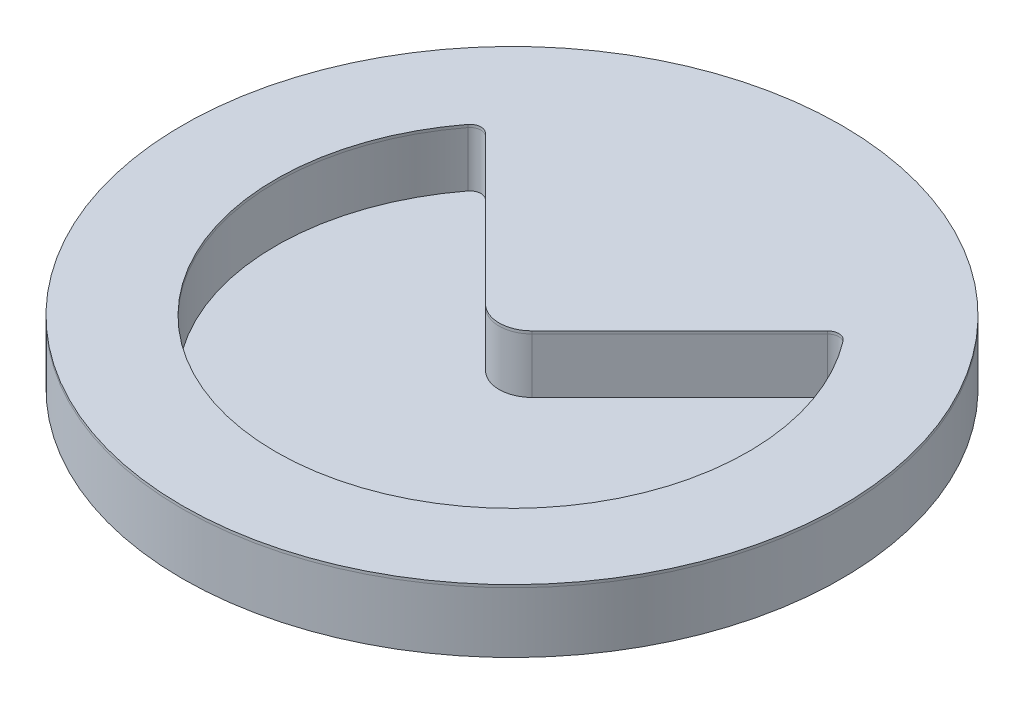
SolidWorks part; units mm, degrees
ref_plane "Front" through (0, 0, 0) normal (0, 0, 1) x (1, 0, 0)
ref_plane "Top" through (0, 0, 0) normal (0, 1, 0) x (1, 0, 0)
ref_plane "Right" through (0, 0, 0) normal (1, 0, 0) x (0, 0, -1)
sketch "Sketch1" plane through (0, 0, 0) normal (0, 1, 0) x (1, 0, 0)
  line L0 (0, 69.6036) -> (0, -75.338) construction
  line L1 (-29.7375, 27.7375) -> (-2.8284, 0.8284)
  line L2 (2.8284, 0.8284) -> (29.7375, 27.7375)
  circle A0 centre (0, 0) radius 60
  arc A1 (-35.7431, 27.3392) -> (35.7431, 27.3392) centre (0, 0) ccw
  arc A2 (29.7375, 27.7375) -> (35.7431, 27.3392) centre (32.5659, 24.9091) cw
  arc A3 (-2.8284, 0.8284) -> (2.8284, 0.8284) centre (0, 3.6569) ccw
  arc A4 (-29.7375, 27.7375) -> (-35.7431, 27.3392) centre (-32.5659, 24.9091) ccw
  point P3 (-21.4713, 39.5472)
  point P8 (0, 0)
  point P14 (0, -2)
  dimension "D1" = 120
  dimension "D2" = 45
  dimension "D5" = 4
  dimension "D3" = 2
  dimension "D4" = 90
extrude "Extrude-Thin1" add sketch "Sketch1" along normal blind 10 thin thin type one direction reverse wall 2
sketch "Sketch2" plane through (0, 0, 0) normal (0, 1, 0) x (1, 0, 0)
  circle A0 centre (0, 0) radius 60
extrude "Boss-Extrude1" add sketch "Sketch2" against normal blind 1
sketch "Sketch4" plane through (0, 10, 0) normal (0, 1, 0) x (1, 0, 0)
  line L4 (-4.2426, -0.5858) -> (-31.1517, 26.3233) construction
  line L5 (31.1517, 26.3233) -> (4.2426, -0.5858) construction
  line L6 (-4.2426, -0.5858) -> (-31.1517, 26.3233)
  line L7 (31.1517, 26.3233) -> (4.2426, -0.5858)
  circle A0 centre (0, 0) radius 60 construction
  circle A2 centre (0, 0) radius 60
  arc A4 (-31.1517, 26.3233) -> (-34.1545, 26.1241) centre (-32.5659, 24.9091) ccw construction
  arc A5 (-34.1545, 26.1241) -> (34.1545, 26.1241) centre (0, 0) ccw construction
  arc A6 (34.1545, 26.1241) -> (31.1517, 26.3233) centre (32.5659, 24.9091) ccw construction
  arc A7 (-4.2426, -0.5858) -> (4.2426, -0.5858) centre (0, 3.6569) ccw construction
  arc A8 (-31.1517, 26.3233) -> (-34.1545, 26.1241) centre (-32.5659, 24.9091) ccw
  arc A9 (-34.1545, 26.1241) -> (34.1545, 26.1241) centre (0, 0) ccw
  arc A10 (34.1545, 26.1241) -> (31.1517, 26.3233) centre (32.5659, 24.9091) ccw
  arc A11 (-4.2426, -0.5858) -> (4.2426, -0.5858) centre (0, 3.6569) ccw
extrude "Boss-Extrude3" add sketch "Sketch4" along normal blind 0.5 separate body
